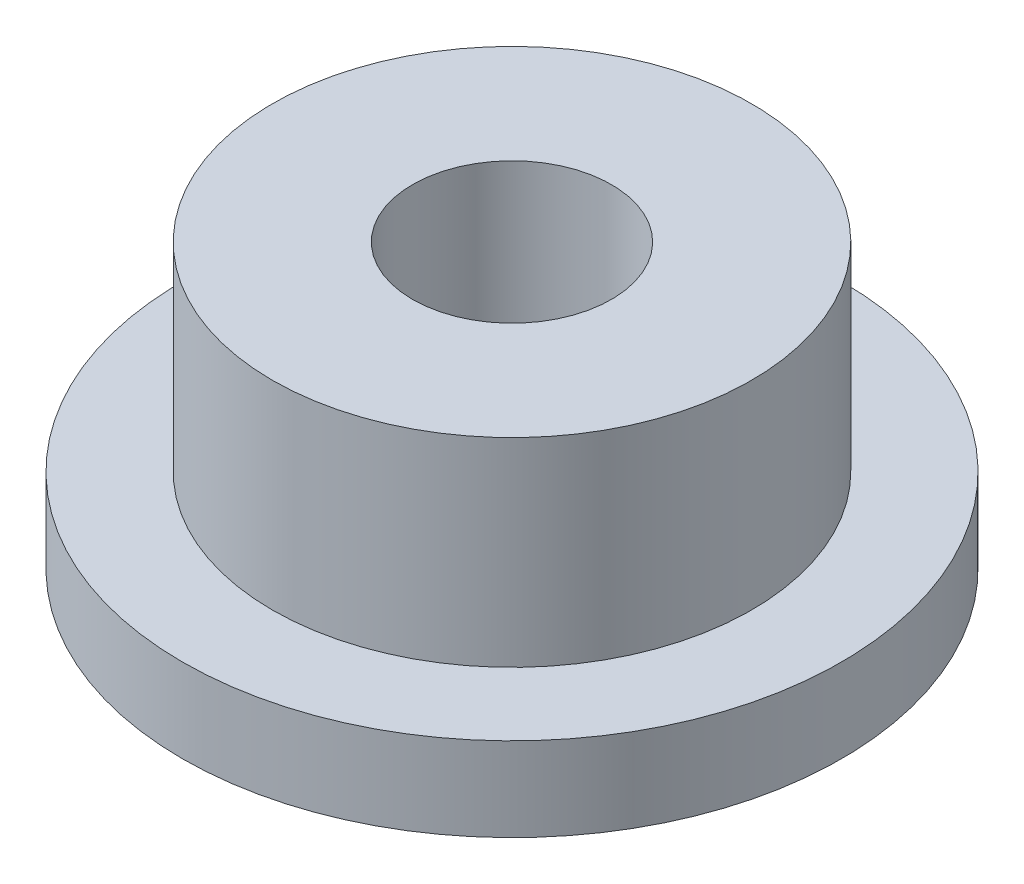
SolidWorks part; units mm, degrees
ref_plane "Front Plane" through (0, 0, 0) normal (0, 0, 1) x (1, 0, 0)
ref_plane "Top Plane" through (0, 0, 0) normal (0, 1, 0) x (1, 0, 0)
ref_plane "Right Plane" through (0, 0, 0) normal (1, 0, 0) x (0, 0, -1)
ref_plane "Plane1" through (0, 0, 0) normal (0, 0, -1) x (-1, 0, 0)
sketch "Sketch5" plane through (0, 0, 0) normal (0, 0, -1) x (-1, 0, 0)
  line L0 (-21.0344, 1) -> (-8.5, 1)
  line L1 (-8.5, 1) -> (-8.5, 0)
  line L2 (-8.5, 0) -> (-6.35, 0)
  line L3 (-6.35, 0) -> (-6.35, 19.05)
  line L4 (-6.35, 19.05) -> (-15.2908, 19.05)
  line L5 (-15.2908, 19.05) -> (-15.2908, 6.35)
  line L6 (-15.2908, 6.35) -> (-21.0344, 6.35)
  line L7 (-21.0344, 6.35) -> (-21.0344, 1)
  line L8 (0, 0) -> (0, 19.05) construction
revolve "Revolve2" add sketch "Sketch5" angle 360 about L8 reverse direction yes
sketch "Sketch7" plane through (0, 0, 0) normal (0, 0, 1) x (1, 0, 0)
  line L0 (6.35, 0) -> (0, 0)
  line L1 (0, 0) -> (0, -6.35)
  line L2 (0, -6.35) -> (6.35, -6.35)
  line L3 (6.35, -6.35) -> (6.35, 0)
  line L4 (0, 0) -> (0, -6.35) construction
revolve "Revolve3" add sketch "Sketch7" angle 360 about L1 reverse direction yes
